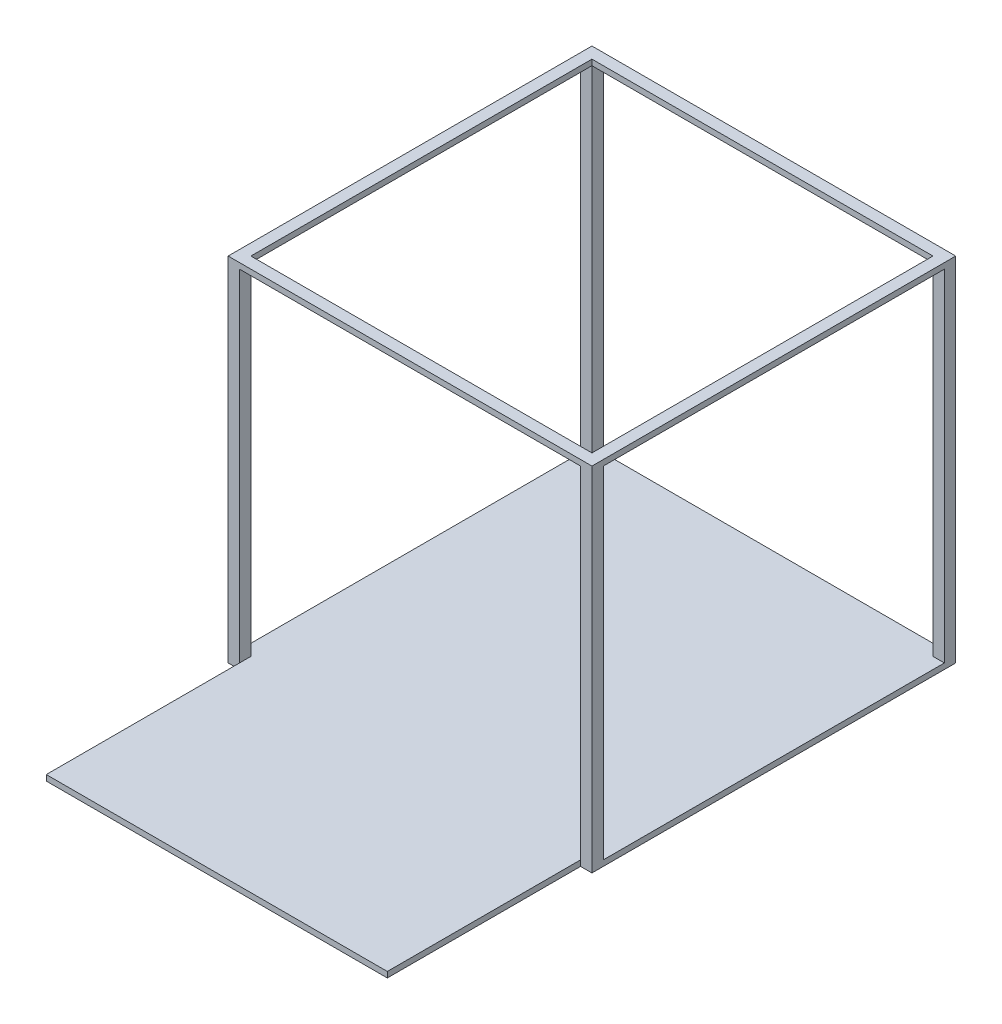
SolidWorks part; units mm, degrees
ref_plane "Front Plane" through (0, 0, 0) normal (0, 0, 1) x (1, 0, 0)
ref_plane "Top Plane" through (0, 0, 0) normal (0, 1, 0) x (1, 0, 0)
ref_plane "Right Plane" through (0, 0, 0) normal (1, 0, 0) x (0, 0, -1)
sketch "Sketch1" plane through (0, 0, 0) normal (0, 1, 0) x (1, 0, 0)
  line L1 (-203.2, -203.2) -> (203.2, -203.2)
  line L2 (-203.2, -203.2) -> (-203.2, 203.2)
  line L3 (-203.2, 203.2) -> (203.2, 203.2)
  line L4 (203.2, -203.2) -> (203.2, 203.2)
  line L5 (-203.2, -203.2) -> (203.2, 203.2) construction
  line L6 (-203.2, 203.2) -> (203.2, -203.2) construction
  point P0 (0, 0)
  dimension "D1" = 406.4
  dimension "D2" = 406.4
extrude "Boss-Extrude1" add sketch "Sketch1" along normal blind 6.35
sketch "Sketch2" plane through (0, 6.35, 0) normal (0, 1, 0) x (1, 0, 0)
  line L0 (0, 203.2) -> (0, -203.2) construction
  line L1 (-203.2, 203.2) -> (-190.5, 203.2)
  line L2 (-203.2, 203.2) -> (-203.2, 190.5)
  line L3 (-203.2, 190.5) -> (-190.5, 190.5)
  line L4 (-190.5, 203.2) -> (-190.5, 190.5)
  line L5 (203.2, 203.2) -> (-203.2, 203.2) construction
  line L6 (-203.2, -203.2) -> (203.2, -203.2) construction
  line L7 (-203.2, 0) -> (203.2, 0) construction
  line L8 (-203.2, 203.2) -> (-203.2, -203.2) construction
  line L9 (203.2, -203.2) -> (203.2, 203.2) construction
  line L10 (190.5, 203.2) -> (190.5, 190.5)
  line L11 (203.2, 190.5) -> (190.5, 190.5)
  line L12 (203.2, 203.2) -> (203.2, 190.5)
  line L13 (203.2, 203.2) -> (190.5, 203.2)
  line L14 (203.2, -203.2) -> (190.5, -203.2)
  line L15 (203.2, -203.2) -> (203.2, -190.5)
  line L16 (203.2, -190.5) -> (190.5, -190.5)
  line L17 (190.5, -203.2) -> (190.5, -190.5)
  line L18 (-190.5, -203.2) -> (-190.5, -190.5)
  line L19 (-203.2, -190.5) -> (-190.5, -190.5)
  line L20 (-203.2, -203.2) -> (-203.2, -190.5)
  line L21 (-203.2, -203.2) -> (-190.5, -203.2)
  dimension "D1" = 12.7
  dimension "D2" = 12.7
extrude "Boss-Extrude2" add sketch "Sketch2" along normal blind 381
sketch "Sketch3" plane through (0, 387.35, 0) normal (0, 1, 0) x (1, 0, 0)
  line L0 (203.2, -190.5) -> (190.5, -190.5) construction
  line L1 (-203.2, 203.2) -> (203.2, 203.2)
  line L2 (-203.2, 203.2) -> (-203.2, -203.2)
  line L3 (-203.2, -203.2) -> (203.2, -203.2)
  line L4 (203.2, 203.2) -> (203.2, -203.2)
  line L5 (-190.5, 190.5) -> (190.5, 190.5)
  line L6 (-190.5, 190.5) -> (-190.5, -190.5)
  line L7 (-190.5, -190.5) -> (190.5, -190.5)
  line L8 (190.5, 190.5) -> (190.5, -190.5)
  line L9 (190.5, -190.5) -> (190.5, -203.2) construction
extrude "Boss-Extrude3" add sketch "Sketch3" along normal blind 6.35
sketch "Sketch4" plane through (0, 6.35, 0) normal (0, 1, 0) x (1, 0, 0)
  line L0 (190.5, -190.5) -> (190.5, -203.2) construction
  line L1 (-190.5, -190.5) -> (190.5, -190.5)
  line L2 (-190.5, -190.5) -> (-190.5, -419.1)
  line L3 (-190.5, -419.1) -> (190.5, -419.1)
  line L4 (190.5, -190.5) -> (190.5, -419.1)
  line L5 (-203.2, 190.5) -> (-190.5, 190.5) construction
  dimension "D1" = 609.6
extrude "Boss-Extrude4" add sketch "Sketch4" against normal blind 6.35
ref_plane "Plane1" through (0, 793.75, 0) normal (0, 1, 0) x (1, 0, 0)
sketch "Sketch5" plane through (0, 793.75, 0) normal (0, 1, 0) x (1, 0, 0)
  line L0 (-190.5, -419.1) -> (190.5, -419.1) construction
  line L1 (-203.2, 203.2) -> (203.2, 203.2)
  line L2 (-203.2, 203.2) -> (-203.2, -431.8)
  line L3 (-203.2, -431.8) -> (203.2, -431.8)
  line L4 (203.2, 203.2) -> (203.2, -431.8)
  line L6 (-190.5, 190.5) -> (190.5, 190.5)
  line L7 (-190.5, 190.5) -> (-190.5, -419.1)
  line L8 (-190.5, -419.1) -> (190.5, -419.1)
  line L9 (190.5, 190.5) -> (190.5, -419.1)
  dimension "D1" = 12.7
extrude "Boss-Extrude5" [suppressed] add sketch "Sketch5" along normal blind 6.35 separate body
